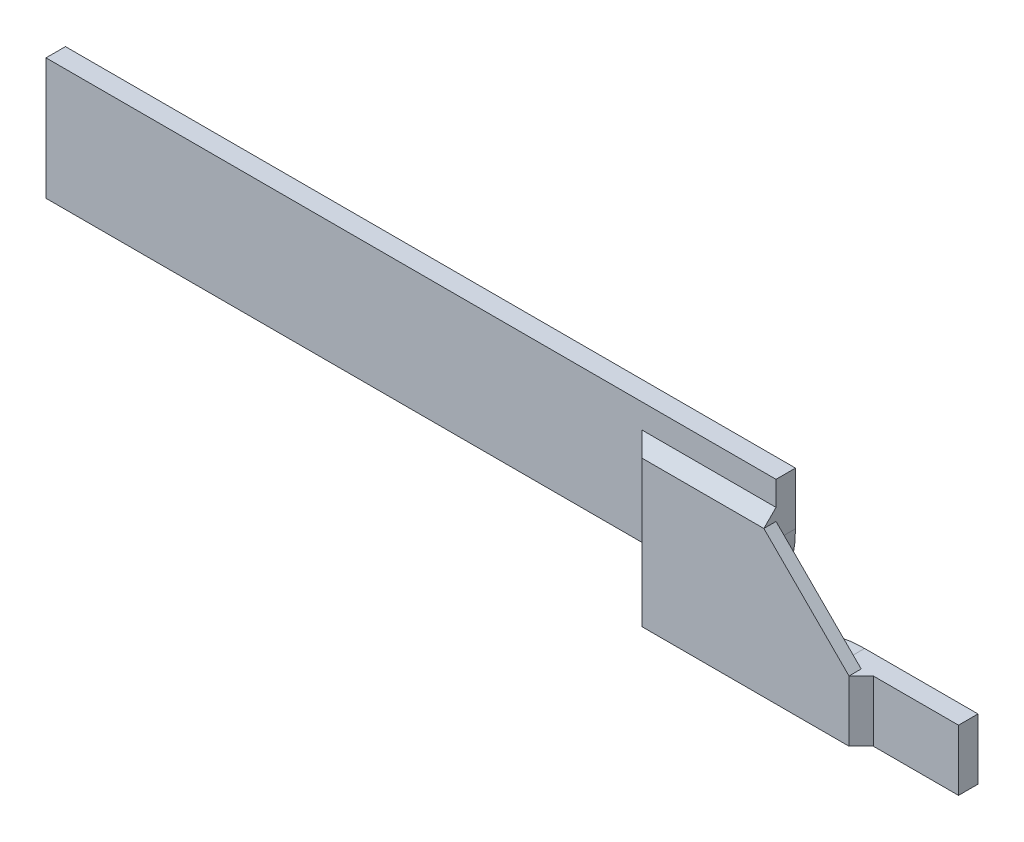
SolidWorks part; units mm, degrees
ref_plane "Plano frontal" through (0, 0, 0) normal (0, 0, 1) x (1, 0, 0)
ref_plane "Plano superior" through (0, 0, 0) normal (0, 1, 0) x (1, 0, 0)
ref_plane "Plano direito" through (0, 0, 0) normal (1, 0, 0) x (0, 0, -1)
sketch "Esboço1" plane through (0, 0, 0) normal (0, 0, 1) x (1, 0, 0)
  line L0 (0, 0) -> (50, 0)
  line L1 (50, 0) -> (50, -5)
  line L2 (50, -5) -> (75, -5)
  line L3 (75, -5) -> (75, 0)
  line L4 (75, 0) -> (61.5, 0)
  line L5 (60, 1.5) -> (60, 10)
  line L6 (60, 10) -> (0, 10)
  line L7 (0, 10) -> (0, 0)
  arc A0 (60, 1.5) -> (61.5, 0) centre (60, 0) ccw
  point P10 (0, 0)
  point P12 (0, 0)
  dimension "D6" = 1.5
  dimension "D1" = 50
  dimension "D2" = 10
  dimension "D3" = 5
  dimension "D4" = 15
  dimension "D5" = 10
extrude "Ressalto-extrusão1" add sketch "Esboço1" along normal blind 1.6
sketch "Esboço2" plane through (0, 0, 1.6) normal (0, 0, 1) x (1, 0, 0)
  line L0 (60, 7) -> (67, 0)
  line L1 (60, 1.5) -> (60, 10) construction
  line L2 (75, 0) -> (61.5, 0) construction
  line L3 (67, 0) -> (67, -5)
  line L4 (50, -5) -> (75, -5) construction
  line L5 (67, -5) -> (50, -5)
  line L6 (50, -5) -> (50, 7)
  line L7 (50, 7) -> (60, 7)
  line L8 (60, 7) -> (60, 0) construction
  line L9 (60, 0) -> (67, 0) construction
  dimension "D1" = 7
extrude "Ressalto-extrusão2" add sketch "Esboço2" along normal blind 1
chamfer "Chanfro1" distance 1 angle 45 3 edges at (55, 7, 1.6) (50, 3.5, 1.6) (67, -2.5, 1.6)
fillet "Filete1" radius 10 2 edges at (61.5, 0, 0.8) (60, 1.5, 0.8)
